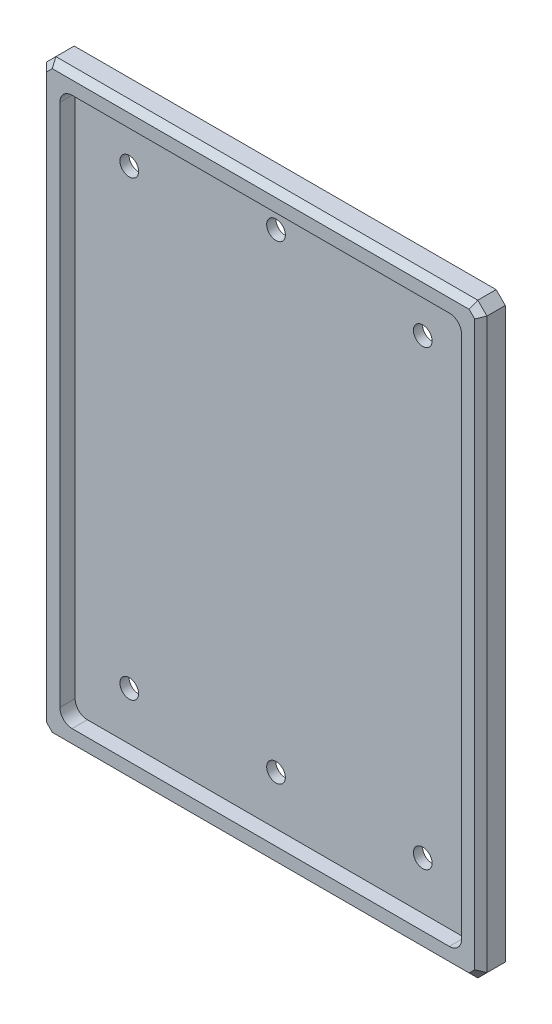
SolidWorks part; units mm, degrees
material "AISI 304"
ref_plane "Front Plane" through (0, 0, 0) normal (0, 0, 1) x (1, 0, 0)
ref_plane "Top Plane" through (0, 0, 0) normal (0, 1, 0) x (1, 0, 0)
ref_plane "Right Plane" through (0, 0, 0) normal (1, 0, 0) x (0, 0, -1)
sketch "Sketch1" plane through (0, 0, 0) normal (0, 0, 1) x (1, 0, 0)
  line L1 (114.3, -152.4) -> (-114.3, -152.4)
  line L2 (114.3, -152.4) -> (114.3, 152.4)
  line L3 (114.3, 152.4) -> (-114.3, 152.4)
  line L4 (-114.3, -152.4) -> (-114.3, 152.4)
  line L5 (114.3, -152.4) -> (-114.3, 152.4) construction
  line L6 (114.3, 152.4) -> (-114.3, -152.4) construction
  point P0 (0, 0)
  dimension "D1" = 228.6
  dimension "D2" = 304.8
extrude "Boss-Extrude1" add sketch "Sketch1" along normal blind 12.7
sketch "Sketch2" plane through (0, 0, 12.7) normal (0, 0, 1) x (1, 0, 0)
  line L0 (-114.3, 152.4) -> (-114.3, -152.4) construction
  line L1 (97.95, -142.4) -> (-97.95, -142.4)
  line L2 (104.3, -136.05) -> (104.3, 136.05)
  line L3 (97.95, 142.4) -> (-97.95, 142.4)
  line L4 (-104.3, -136.05) -> (-104.3, 136.05)
  line L5 (104.3, -142.4) -> (-104.3, 142.4) construction
  line L6 (104.3, 142.4) -> (-104.3, -142.4) construction
  line L7 (114.3, 152.4) -> (-114.3, 152.4) construction
  arc A0 (-97.95, -142.4) -> (-104.3, -136.05) centre (-97.95, -136.05) cw
  arc A1 (97.95, -142.4) -> (104.3, -136.05) centre (97.95, -136.05) ccw
  arc A2 (104.3, 136.05) -> (97.95, 142.4) centre (97.95, 136.05) ccw
  arc A3 (-97.95, 142.4) -> (-104.3, 136.05) centre (-97.95, 136.05) ccw
  point P0 (0, 0)
  dimension "D3" = 6.35
  dimension "D1" = 10
  dimension "D2" = 10
extrude "Cut-Extrude1" cut sketch "Sketch2" against normal blind 7.9375
sketch "Sketch4" plane through (0, 0, 4.7625) normal (0, 0, 1) x (1, 0, 0)
  line L0 (114.3, 152.4) -> (-114.3, 152.4) construction
  line L4 (-114.3, 152.4) -> (-114.3, -152.4) construction
  line L5 (114.3, -152.4) -> (114.3, 152.4) construction
  line L6 (-114.3, -152.4) -> (114.3, -152.4) construction
  line L8 (-97.95, -142.4) -> (97.95, -142.4) construction
  circle A0 centre (-76.2, 117.4) radius 4.85
  circle A1 centre (76.2, 117.4) radius 4.85
  circle A2 centre (-76.2, -117.4) radius 4.85
  circle A3 centre (76.2, -117.4) radius 4.85
  circle A4 centre (0, 126.925) radius 4.85
  circle A5 centre (0, -117) radius 4.85
  dimension "D1" = 9.7
  dimension "D2" = 9.7
  dimension "D3" = 9.7
  dimension "D4" = 9.7
  dimension "D13" = 9.7
  dimension "D14" = 9.7
  dimension "D15" = 35
  dimension "D5" = 9.525
  dimension "D6" = 38.1
  dimension "D7" = 38.1
  dimension "D8" = 0
  dimension "D9" = 35
  dimension "D10" = 38.1
  dimension "D11" = 38.1
  dimension "D12" = 35
  dimension "D16" = 25.4
extrude "Cut-Extrude2" cut sketch "Sketch4" against normal through all
hole_wizard "M4x0.7 Tapped Hole1" positions "Sketch8" profile "Sketch9" tap size "M4x0.7" standard "ANSI Metric"
sketch "Sketch8" plane through (0, 0, 0) normal (0, 0, -1) x (-1, 0, 0)
  line L0 (114.3, -152.4) -> (-114.3, -152.4) construction
  line L1 (-114.3, -152.4) -> (-114.3, 152.4) construction
  point P0 (-111.125, -102.4)
  point P2 (-111.125, 0)
  point P4 (-111.125, 113.6)
  point P14 (-114.3, 0)
  dimension "D1" = 266
  dimension "D2" = 3.175
  dimension "D3" = 50
sketch "Sketch9" plane through (111.125, -102.4, 0) normal (1, 0, 0) x (0, 1, 0)
  line L0 (0, 0) -> (0, 6.3914)
  line L1 (0, 6.3914) -> (1.65, 5.4)
  line L2 (1.65, 5.4) -> (1.65, 0)
  line L5 (1.65, 0) -> (0, 0)
  line L10 (0, 6.3914) -> (-1.65, 5.4) construction
  line L11 (0, -6.35) -> (0, 107.95) construction
  dimension "Tap Drill Dia." = 3.3
  dimension "Tap Drill Depth" = 5.4
  dimension "Drill Angle" = 118
cosmetic thread "Hole Thread1" parameters "D1"=3, "D2"=4.3
cosmetic thread "Hole Thread2" parameters "D1"=3, "D2"=4.3
cosmetic thread "Hole Thread3" parameters "D1"=3, "D2"=4.3
chamfer "Chamfer1" distance 4.7625 angle 45 4 edges at (-114.3, -152.4, 6.35) (114.3, -152.4, 6.35) (-114.3, 152.4, 6.35) (114.3, 152.4, 6.35)
chamfer "Chamfer2" distance 3.175 angle 45 8 edges at (-111.9188, 150.0187, 12.7) (0, 152.4, 12.7) (111.9187, 150.0187, 12.7) (114.3, 0, 12.7) (111.9187, -150.0188, 12.7) (0, -152.4, 12.7) (-111.9188, -150.0188, 12.7) (-114.3, 0, 12.7)
